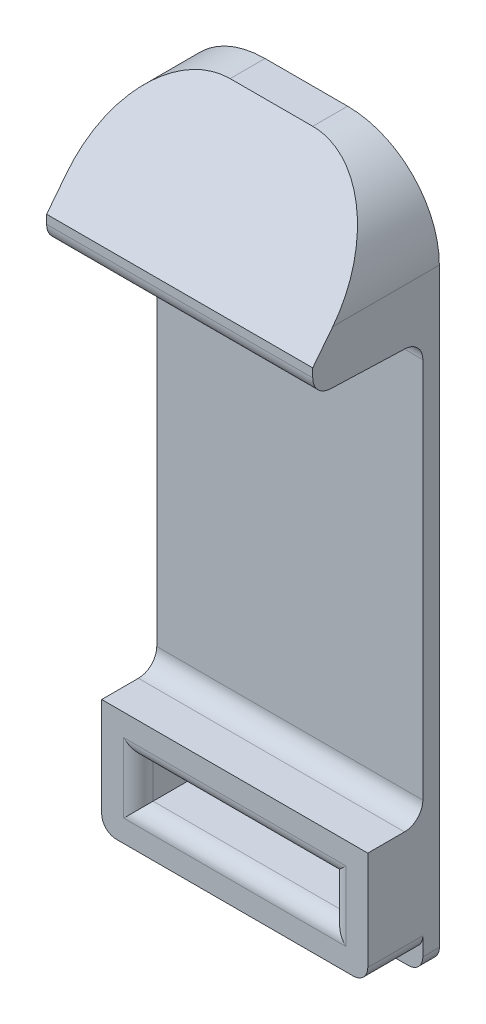
SolidWorks part; units mm, degrees
ref_plane "Front Plane" through (0, 0, 0) normal (0, 0, 1) x (1, 0, 0)
ref_plane "Top Plane" through (0, 0, 0) normal (0, 1, 0) x (1, 0, 0)
ref_plane "Right Plane" through (0, 0, 0) normal (1, 0, 0) x (0, 0, -1)
sketch "Sketch1" plane through (0, 0, 0) normal (0, 0, 1) x (1, 0, 0)
  line L0 (-5.25, 0) -> (5.25, 0)
  line L1 (-5.25, 0) -> (-5.25, 2.2)
  line L2 (5.25, 0) -> (5.25, 2.2)
  line L3 (-5.25, 2.2) -> (5.25, 2.2)
  line L4 (55, 0) -> (-55, 0) construction
  line L5 (0, -55) -> (0, 55) construction
  line L6 (-7.25, -3) -> (7.25, -3)
  line L7 (-7.25, -3) -> (-7.25, 35)
  line L8 (7.25, -3) -> (7.25, 35)
  line L9 (-7.25, 35) -> (7.25, 35)
  point P4 (0, 2.2)
  point P7 (0, -3)
  dimension "D1" = 2.2
  dimension "D2" = 10.5
  dimension "D3" = 35
  dimension "D4" = 3
  dimension "D5" = 14.5
extrude "Boss-Extrude1" add sketch "Sketch1" along normal blind 0.9
sketch "Sketch2" plane through (0, 0, 0.9) normal (0, 0, 1) x (1, 0, 0)
  line L0 (-7.25, 35) -> (7.25, 35)
  line L1 (-7.25, 35) -> (-7.25, 26.95)
  line L2 (7.25, 35) -> (7.25, 26.95)
  line L3 (-7.25, 26.95) -> (7.25, 26.95)
  line L4 (5.25, 2.2) -> (-5.25, 2.2) construction
  line L5 (-5.25, 0) -> (5.25, 0) construction
  line L6 (-5.25, 2.2) -> (-5.25, 0) construction
  line L7 (5.25, 0) -> (5.25, 2.2) construction
  line L8 (-5.25, 0) -> (5.25, 0)
  line L9 (-5.25, 2.2) -> (-5.25, 0)
  line L10 (5.25, 2.2) -> (-5.25, 2.2)
  line L11 (5.25, 0) -> (5.25, 2.2)
  line L12 (-7.25, -2) -> (7.25, -2)
  line L13 (7.25, -2) -> (7.25, 4.2)
  line L14 (7.25, 4.2) -> (-7.25, 4.2)
  line L15 (-7.25, 4.2) -> (-7.25, -2)
  line M5 (-7.25, 35) -> (-7.25, -3)
  line M7 (7.25, -3) -> (7.25, 35)
  line M8 (7.25, 35) -> (-7.25, 35)
  line M9 (-5.25, 0) -> (-5.25, 2.2)
  line M10 (-5.25, 2.2) -> (5.25, 2.2)
  line M11 (5.25, 2.2) -> (5.25, 0)
  line M12 (5.25, 0) -> (-5.25, 0)
  dimension "D1" = 24.75
  dimension "D2" = 2
extrude "Boss-Extrude2" add sketch "Sketch2" along normal blind 6 contours L3 M5 M7 M8 region at (0, 30.975, 0.9)
draft "Draft1" type of draft neutral plane draft angle 2 faces to draft 1 face at (0, 26.95, 3.9) neutral plane through (0, 0, 0.9) neutral plane normal (0, 0, 1) parameters "D1"=2
extrude "Boss-Extrude3" add sketch "Sketch2<3>" along normal blind 3 contours L14 L12 M7 M5 M12 M9 M10 M11 region at (0, 4.0423, 0.9)
sketch "Sketch2<3>" plane through (0, 0, 0.9) normal (0, 0, 1) x (1, 0, 0) same geometry as "Sketch2"
chamfer "Chamfer1" distance 5 angle 52 1 edges at (0, 35, 6.9) first distance on face at (0, 35, 3.45)
fillet "Fillet2" radius 1 1 edges at (0, 27.1595, 6.9)
fillet "Fillet3" radius 1 2 edges at (0, 26.95, 0.9) (0, 4.2, 0.9)
fillet "Fillet4" radius 5 2 edges at (7.25, 35, 0.95) (-7.25, 35, 0.95)
fillet "Fillet5" radius 0.8 8 edges at (0, 0, 3.9) (5.25, 1.1, 3.9) (-5.25, 1.1, 3.9) (0, 2.2, 3.9) (7.25, -2, 2.4) (7.25, -3, 0.45) (-7.25, -2, 2.4) (-7.25, -3, 0.45)
